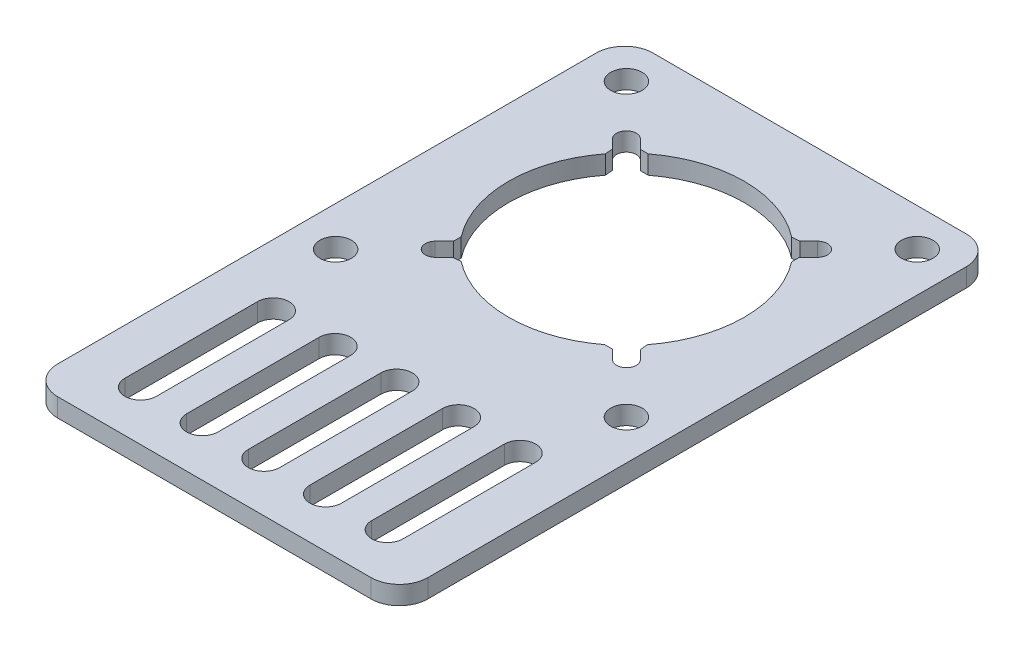
SolidWorks part; units mm, degrees
material "6061-T6 (SS)"
ref_plane "Front Plane" through (0, 0, 0) normal (0, 0, 1) x (1, 0, 0)
ref_plane "Top Plane" through (0, 0, 0) normal (0, 1, 0) x (1, 0, 0)
ref_plane "Right Plane" through (0, 0, 0) normal (1, 0, 0) x (0, 0, -1)
sketch "Sketch1" plane through (0, 0, 0) normal (0, 1, 0) x (1, 0, 0)
  line L0 (0, 0) -> (30, 0) construction
  line L1 (25.4, -66.8) -> (-25.4, -66.8)
  line L2 (30, -62.2) -> (30, 25.1)
  line L3 (25.4, 29.7) -> (-25.4, 29.7)
  line L4 (-30, -62.2) -> (-30, 25.1)
  line L5 (0, 29.7) -> (0, 0) construction
  line L6 (20, -58.75) -> (20, -37.25) construction
  line L7 (17.45, -58.75) -> (17.45, -37.25)
  line L8 (22.55, -58.75) -> (22.55, -37.25)
  line L9 (10, -58.75) -> (10, -37.25) construction
  line L10 (7.45, -58.75) -> (7.45, -37.25)
  line L11 (12.55, -58.75) -> (12.55, -37.25)
  line L12 (0, -58.75) -> (0, -37.25) construction
  line L13 (-2.55, -58.75) -> (-2.55, -37.25)
  line L14 (2.55, -58.75) -> (2.55, -37.25)
  line L15 (-10, -58.75) -> (-10, -37.25) construction
  line L16 (-12.55, -58.75) -> (-12.55, -37.25)
  line L17 (-7.45, -58.75) -> (-7.45, -37.25)
  line L18 (-20, -58.75) -> (-20, -37.25) construction
  line L19 (-22.55, -58.75) -> (-22.55, -37.25)
  line L20 (-17.45, -58.75) -> (-17.45, -37.25)
  line L21 (20, -58.75) -> (10, -58.75) construction
  line L22 (0, 0) -> (15.5, 15.5) construction
  line L23 (14.3686, 16.6314) -> (12.3269, 14.5896)
  line L24 (16.6314, 14.3686) -> (14.5896, 12.3269)
  line L25 (-16.6314, 14.3686) -> (-14.5896, 12.3269)
  line L26 (-14.3686, 16.6314) -> (-12.3269, 14.5896)
  line L27 (-16.6314, -14.3686) -> (-14.5896, -12.3269)
  line L28 (-14.3686, -16.6314) -> (-12.3269, -14.5896)
  line L29 (16.6314, -14.3686) -> (14.5896, -12.3269)
  line L30 (14.3686, -16.6314) -> (12.3269, -14.5896)
  arc A0 (-25.4, -66.8) -> (-30, -62.2) centre (-25.4, -62.2) cw
  arc A1 (25.4, -66.8) -> (30, -62.2) centre (25.4, -62.2) ccw
  arc A2 (30, 25.1) -> (25.4, 29.7) centre (25.4, 25.1) ccw
  arc A3 (-25.4, 29.7) -> (-30, 25.1) centre (-25.4, 25.1) ccw
  circle A4 centre (-23.57, 23.57) radius 2.55
  circle A5 centre (23.57, 23.57) radius 2.55
  circle A6 centre (23.57, -23.57) radius 2.55
  circle A7 centre (-23.57, -23.57) radius 2.55
  arc A8 (12.3269, 14.5896) -> (-12.3269, 14.5896) centre (0, 0) ccw
  arc A9 (17.45, -58.75) -> (22.55, -58.75) centre (20, -58.75) ccw
  arc A10 (22.55, -37.25) -> (17.45, -37.25) centre (20, -37.25) ccw
  arc A11 (7.45, -58.75) -> (12.55, -58.75) centre (10, -58.75) ccw
  arc A12 (12.55, -37.25) -> (7.45, -37.25) centre (10, -37.25) ccw
  arc A13 (-2.55, -58.75) -> (2.55, -58.75) centre (0, -58.75) ccw
  arc A14 (2.55, -37.25) -> (-2.55, -37.25) centre (0, -37.25) ccw
  arc A15 (-12.55, -58.75) -> (-7.45, -58.75) centre (-10, -58.75) ccw
  arc A16 (-7.45, -37.25) -> (-12.55, -37.25) centre (-10, -37.25) ccw
  arc A17 (-22.55, -58.75) -> (-17.45, -58.75) centre (-20, -58.75) ccw
  arc A18 (-17.45, -37.25) -> (-22.55, -37.25) centre (-20, -37.25) ccw
  arc A19 (-14.3686, 16.6314) -> (-16.6314, 14.3686) centre (-15.5, 15.5) ccw
  arc A20 (14.3686, 16.6314) -> (16.6314, 14.3686) centre (15.5, 15.5) cw
  arc A21 (14.3686, -16.6314) -> (16.6314, -14.3686) centre (15.5, -15.5) ccw
  arc A22 (-14.3686, -16.6314) -> (-16.6314, -14.3686) centre (-15.5, -15.5) cw
  arc A23 (-14.5896, 12.3269) -> (-14.5896, -12.3269) centre (0, 0) ccw
  arc A24 (-12.3269, -14.5896) -> (12.3269, -14.5896) centre (0, 0) ccw
  arc A25 (14.5896, -12.3269) -> (14.5896, 12.3269) centre (0, 0) ccw
  point P26 (20, -48)
  point P36 (10, -48)
  point P43 (0, -48)
  point P50 (-10, -48)
  point P57 (-20, -48)
  dimension "D2" = 4.6
  dimension "D3" = 66.8
  dimension "D5" = 47.14
  dimension "D7" = 5.5
  dimension "D10" = 10
  dimension "D4" = 5.1
  dimension "D8" = 26.6
  dimension "D14" = 38.2
  dimension "D15" = 3.2
  dimension "D17" = 31
  dimension "D1" = 96.5
  dimension "D6" = 47.14
  dimension "D9" = 60
  dimension "D11" = 5.1
  dimension "D12" = 5
  dimension "D13" = 10
  dimension "D16" = 45
extrude "Boss-Extrude1" add sketch "Sketch1" along normal blind 3
chamfer "Chamfer1" distance 0.8 angle 45 8 edges at (12.3269, 1.5, 14.5896) (14.5896, 1.5, 12.3269) (-12.3269, 1.5, 14.5896) (-14.5896, 1.5, 12.3269) (-14.5896, 1.5, -12.3269) (-12.3269, 1.5, -14.5896) (12.3269, 1.5, -14.5896) (14.5896, 1.5, -12.3269) first distance on face at (13.3478, 1.5, 15.6105) first distance on face at (16.8448, 1.5, 0) first distance on face at (0, 1.5, 16.8448) first distance on face at (-15.6105, 1.5, 13.3478) first distance on face at (-16.8448, 1.5, 0) first distance on face at (-13.3478, 1.5, -15.6105) first distance on face at (0, 1.5, -16.8448) first distance on face at (15.6105, 1.5, -13.3478)
